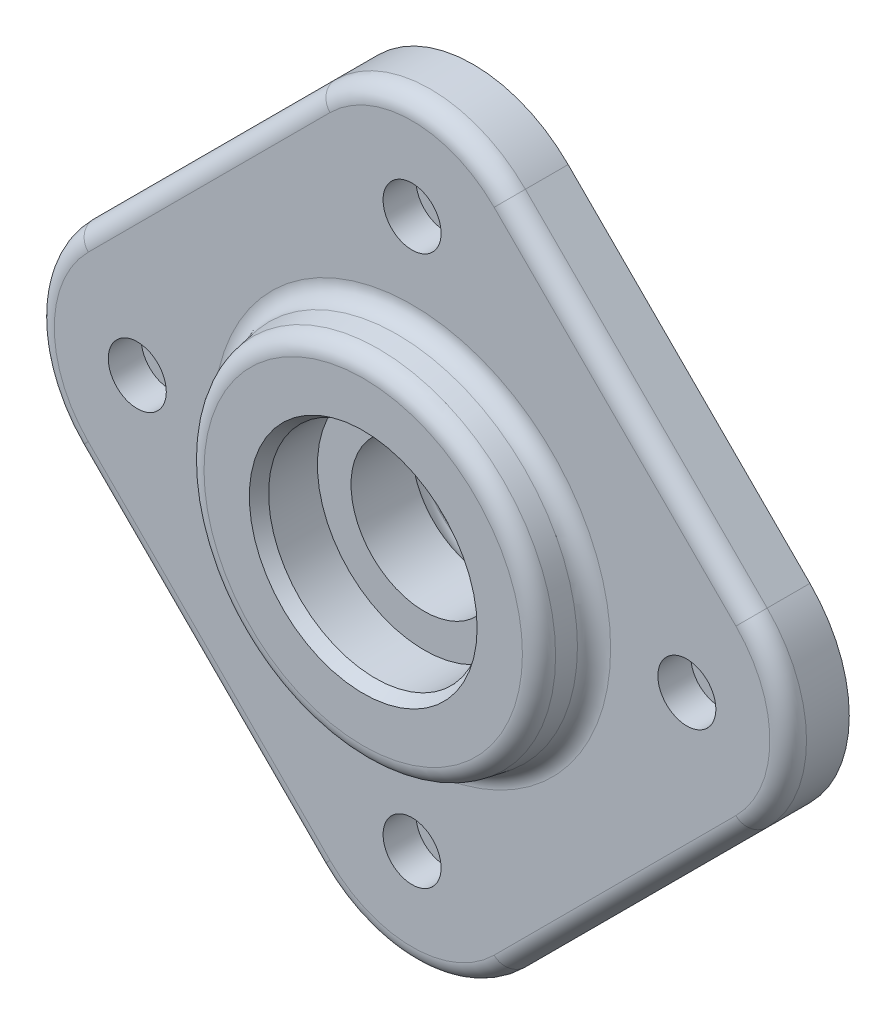
SolidWorks part; units mm, degrees
material "Cast Alloy Steel"
ref_plane "Front Plane" through (0, 0, 0) normal (0, 0, 1) x (1, 0, 0)
ref_plane "Top Plane" through (0, 0, 0) normal (0, 1, 0) x (1, 0, 0)
ref_plane "Right Plane" through (0, 0, 0) normal (1, 0, 0) x (0, 0, -1)
sketch "Sketch1" plane through (0, 0, 0) normal (0, 0, 1) x (1, 0, 0)
  line L0 (-15.5563, 55.1543) -> (-55.1543, 15.5563)
  line L1 (15.5563, 55.1543) -> (55.1543, 15.5563)
  line L2 (-55.1543, -15.5563) -> (-15.5563, -55.1543)
  line L3 (55.1543, -15.5563) -> (15.5563, -55.1543)
  line L4 (0, 70.7107) -> (0, -70.7107) construction
  line L5 (-70.7107, 0) -> (70.7107, 0) construction
  arc A0 (-15.5563, -55.1543) -> (15.5563, -55.1543) centre (0, -39.598) ccw
  arc A1 (-55.1543, 15.5563) -> (-55.1543, -15.5563) centre (-39.598, 0) ccw
  arc A2 (15.5563, 55.1543) -> (-15.5563, 55.1543) centre (0, 39.598) ccw
  arc A3 (55.1543, 15.5563) -> (55.1543, -15.5563) centre (39.598, 0) cw
  point P1 (0, 0)
  dimension "D3" = 22
  dimension "D1" = 100
  dimension "D2" = 100
extrude "Boss-Extrude1" add sketch "Sketch1" along normal blind 10
sketch "Sketch2" plane through (0, 0, 10) normal (0, 0, 1) x (1, 0, 0)
  circle A0 centre (0, 0) radius 30
  dimension "D1" = 60
extrude "Boss-Extrude2" add sketch "Sketch2" along normal blind 8 draft 10
sketch "Sketch4" plane through (0, 0, 0) normal (0, 0, -1) x (-1, 0, 0)
  circle A0 centre (0, 0) radius 17.5
  dimension "D2" = 35
extrude "Boss-Extrude3" add sketch "Sketch4" along normal blind 5
sketch "Sketch3" plane through (0, 0, 18) normal (0, 0, 1) x (1, 0, 0)
  circle A0 centre (0, 0) radius 12
  circle A1 centre (0, 0) radius 17.5
  dimension "D1" = 24
  dimension "D2" = 35
extrude "Cut-Extrude1" cut sketch "Sketch3" against normal through all both and the other way through all contours A0 region at (0, 0, 18)
extrude "Cut-Extrude2" cut sketch "Sketch3<3>" against normal blind 10 contours A1 A0 region at (-17.005, 0, 18)
sketch "Sketch3<3>" plane through (0, 0, 18) normal (0, 0, 1) x (1, 0, 0) same geometry as "Sketch3"
sketch "Sketch5" plane through (0, 0, -5) normal (0, 0, -1) x (-1, 0, 0)
  circle A0 centre (0, 0) radius 14
  dimension "D1" = 28
extrude "Cut-Extrude3" cut sketch "Sketch5" against normal blind 3
sketch "Sketch6" plane through (0, 0, 10) normal (0, 0, 1) x (1, 0, 0)
  line L0 (0, 61.598) -> (0, -61.598) construction
  line L1 (61.598, 0) -> (-61.598, 0) construction
  circle A0 centre (0, 0) radius 45 construction
  arc A1 (15.5563, 55.1543) -> (-15.5563, 55.1543) centre (0, 39.598) ccw construction
  arc A2 (-15.5563, -55.1543) -> (15.5563, -55.1543) centre (0, -39.598) ccw construction
  arc A3 (55.1543, -15.5563) -> (55.1543, 15.5563) centre (39.598, 0) ccw construction
  arc A4 (-55.1543, 15.5563) -> (-55.1543, -15.5563) centre (-39.598, 0) ccw construction
  circle A5 centre (0, 45) radius 2.75
  circle A9 centre (0, 45) radius 4.75
  circle A10 centre (45, 0) radius 4.75
  circle A11 centre (45, 0) radius 2.75
  circle A12 centre (0, -45) radius 4.75
  circle A13 centre (0, -45) radius 2.75
  circle A14 centre (-45, 0) radius 4.75
  circle A15 centre (-45, 0) radius 2.75
  point P22 (-45, 0)
  point P34 (0, 0)
  dimension "D1" = 90
  dimension "D2" = 5.5
  dimension "D3" = 9.5
  dimension "D4" = 4
extrude "Cut-Extrude4" cut sketch "Sketch6" against normal through all both and the other way through all contours A5 | A11 | A13 | A15
extrude "Cut-Extrude5" cut sketch "Sketch6<3>" against normal blind 5.4 contours A14 A15 | A12 A13 | A10 A11 | A9 A5 region at (-4.6156, 45, 10) region at (40.3844, 0, 10) region at (-4.6156, -45, 10) region at (-49.6156, 0, 10)
sketch "Sketch6<3>" plane through (0, 0, 10) normal (0, 0, 1) x (1, 0, 0) same geometry as "Sketch6"
sketch "Sketch7" plane through (0, 0, 0) normal (1, 0, 0) x (0, 0, -1)
  line L0 (-18, 17.5) -> (-16, 17.5)
  line L1 (-18, 28.5894) -> (-18, -28.5894) construction
  line L2 (-18, 17.5) -> (-18, -17.5) construction
  line L3 (-16, 17.5) -> (-18, 18.6547)
  line L4 (-18, 18.6547) -> (-18, 17.5)
  line L5 (-32.7787, 0) -> (13.5302, 0) construction
  dimension "D1" = 30
  dimension "D2" = 17.5
  dimension "D3" = 2
revolve "Cut-Revolve1" cut sketch "Sketch7" angle 360 about L5
fillet "Fillet1" radius 3 2 edges at (30, 0, 10) (28.5894, 0, 18)
fillet "Fillet2" radius 3 8 edges at (0, -61.598, 10) (-35.3553, -35.3553, 10) (-61.598, 0, 10) (-35.3553, 35.3553, 10) (0, 61.598, 10) (35.3553, 35.3553, 10) (61.598, 0, 10) (35.3553, -35.3553, 10)
fillet "Fillet3" radius 3 1 edges at (-14, 0, -2)
fillet "Fillet4" radius 2 1 edges at (-17.5, 0, -5)
